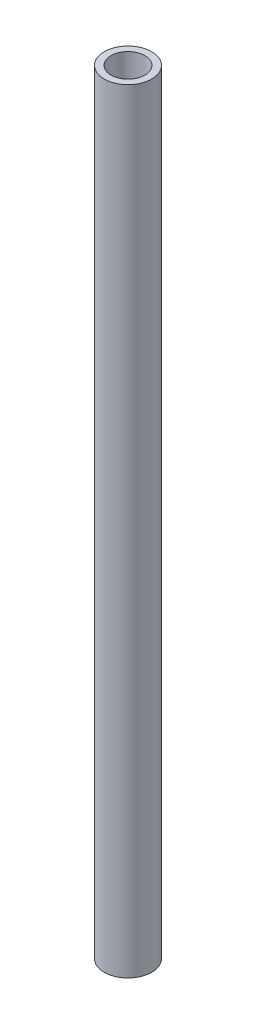
SolidWorks part; units mm, degrees
ref_plane "Płaszczyzna przednia" through (0, 0, 0) normal (0, 0, 1) x (1, 0, 0)
ref_plane "Płaszczyzna górna" through (0, 0, 0) normal (0, 1, 0) x (1, 0, 0)
ref_plane "Płaszczyzna prawa" through (0, 0, 0) normal (1, 0, 0) x (0, 0, -1)
sketch "Sketch1" plane through (0, 0, 0) normal (0, 1, 0) x (1, 0, 0)
  circle A0 centre (0, 0) radius 7
  circle A1 centre (0, 0) radius 4
  dimension "D1" = 14
  dimension "D2" = 3
extrude "Boss-Extrude1" add sketch "Sketch1" along normal blind 228.4
sketch "Sketch2" plane through (0, 228.4, 0) normal (0, 1, 0) x (1, 0, 0)
  circle A1 centre (0, 0) radius 5
  dimension "D1" = 10
extrude "Cut-Extrude1" cut sketch "Sketch2" against normal blind 31
extrude "Cut-Extrude2" cut sketch "Sketch2<2>" along normal blind 31 from surface starting at face at (0, 0, 7)
sketch "Sketch2<2>" plane through (0, 228.4, 0) normal (0, 1, 0) x (1, 0, 0) same geometry as "Sketch2"
equation "\"G\"= 3'grubość ścianki"
equation "\"L\"= 300'długość całkowita"
equation "\"G1\"= 31'głębokość gwintu"
